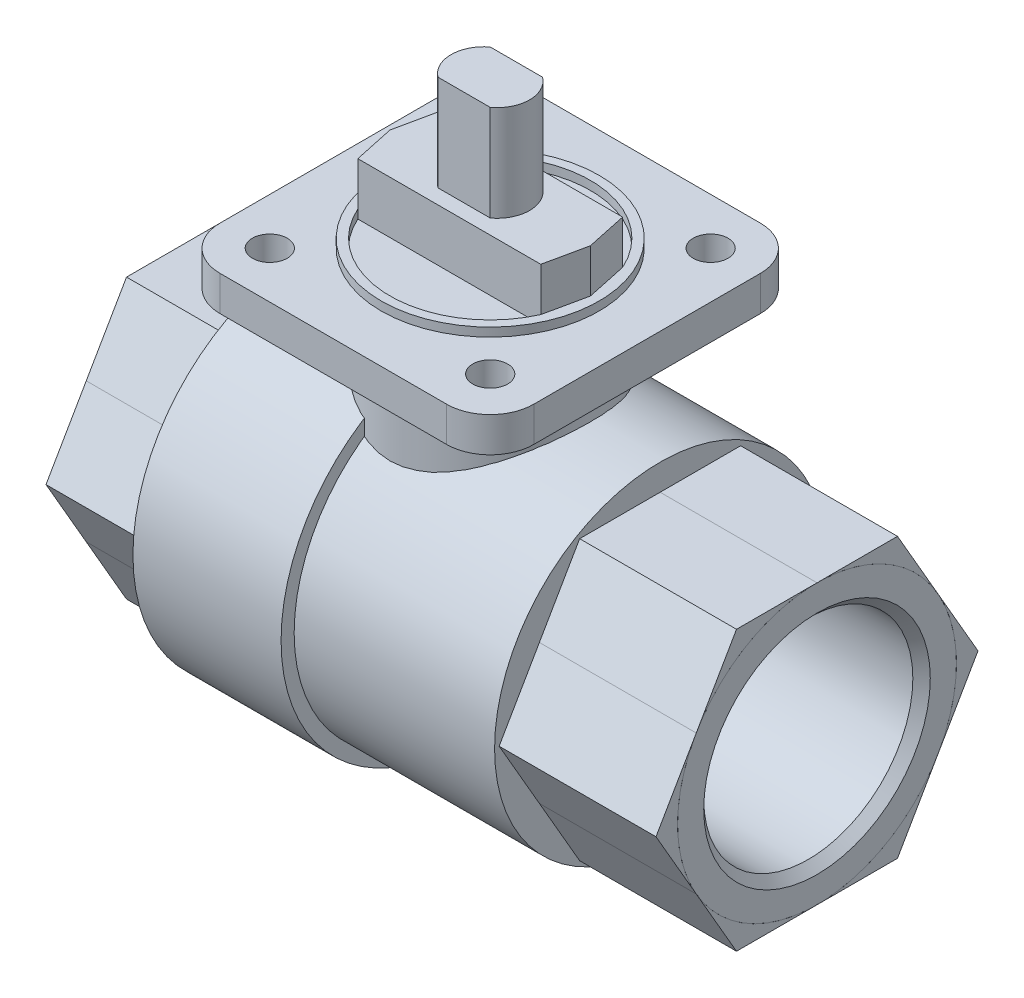
SolidWorks part; units mm, degrees
ref_plane "Front Plane" through (0, 0, 0) normal (0, 0, 1) x (1, 0, 0)
ref_plane "Top Plane" through (0, 0, 0) normal (0, 1, 0) x (1, 0, 0)
ref_plane "Right Plane" through (0, 0, 0) normal (1, 0, 0) x (0, 0, -1)
sketch "Szkic1" plane through (0, 0, 0) normal (0, 0, 1) x (1, 0, 0)
  line L0 (0, 0) -> (0, 32)
  line L1 (0, 32) -> (17, 32)
  line L2 (17, 32) -> (17, 0)
  line L3 (17, 0) -> (0, 0)
  line L4 (17, 32) -> (17, 30)
  line L5 (17, 0) -> (17, 2)
  line L6 (17, 2) -> (47, 2)
  line L7 (47, 2) -> (47, 30)
  line L8 (47, 30) -> (17, 30)
  line L9 (47, 30) -> (47, 32)
  line L10 (47, 32) -> (70, 32)
  line L11 (70, 32) -> (70, 0)
  line L12 (70, 0) -> (47, 0)
  line L13 (47, 0) -> (47, 2)
  line L14 (47, 2) -> (47, 0)
  line L15 (47, 2) -> (47, 30)
  line L16 (17, 2) -> (17, 30)
  line L17 (17, 30) -> (47, 30)
  line L18 (47, 2) -> (17, 2)
  line L19 (47, 2) -> (47, 0)
  line L20 (70, 0) -> (70, 32)
  line L21 (47, 32) -> (47, 30)
  line L22 (47, 32) -> (47, 30)
  line L23 (0, 32) -> (12, 32)
  line L24 (0, 0) -> (11, 0)
  line L25 (0, 32) -> (0, 28)
  line L26 (0, 28) -> (70, 28)
  line L27 (0, 0) -> (0, 4)
  line L28 (0, 4) -> (70, 4)
  line L29 (12, 32) -> (12, 36.5)
  line L30 (12, 36.5) -> (29, 36.5)
  line L31 (0, 16) -> (70, 16)
  line L32 (29, 36.5) -> (29, 35)
  line L33 (29, 35) -> (52, 35)
  line L34 (52, 35) -> (52, 32)
  line L35 (17, 30) -> (17, 26)
  line L36 (17, 26) -> (47, 26)
  line L37 (47, 26) -> (47, 30)
  dimension "D1" = 32
  dimension "D2" = 17
  dimension "D3" = 2
  dimension "D4" = 2
  dimension "D5" = 30
  dimension "D6" = 18
  dimension "D7" = 12
  dimension "D8" = 4
  dimension "D9" = 4
  dimension "D10" = 4.5
  dimension "D11" = 17
  dimension "D12" = 1.5
  dimension "D13" = 23
  dimension "D14" = 70
  dimension "D15" = 4
revolve "Obrót2" add sketch "Szkic1" angle 360 about L31 region at (8.5, 30, 0) region at (32, 27, 0) region at (32, 29, 0) region at (30.573, 33.0493, 0) region at (58.5, 30, 0)
sketch "Szkic2" plane through (0, 0, 0) normal (1, 0, 0) x (0, 0, -1)
  line L1 (18.4752, 16) -> (9.2376, 32)
  line L2 (9.2376, 32) -> (-9.2376, 32)
  line L3 (-9.2376, 32) -> (-18.4752, 16)
  line L4 (-18.4752, 16) -> (-9.2376, 0)
  line L5 (-9.2376, 0) -> (9.2376, 0)
  line L6 (9.2376, 0) -> (18.4752, 16)
  circle A0 centre (0, 16) radius 16
  circle A1 centre (0, 16) radius 16 construction
  dimension "D1" = 16
extrude "Dodanie-wyciągnięcie2" add sketch "Szkic2" along normal blind 70 separate body contours A0 L2 L3 | A0 L3 L4 | A0 L4 L5 | A0 L5 L6 | A0 L6 L1 | A0 L1 L2 region at (0, 16, -16.537) region at (0, 30.3215, -8.2685) region at (0, 1.6785, -8.2685) region at (0, 30.3215, 8.2685) region at (0, 1.6785, 8.2685) region at (0, 16, 16.537)
fillet "Zaokrąglenie2" radius 1 1 edges at (0, 16, 12)
chamfer "Sfazowanie1" distance 1 angle 45 1 edges at (70, 16, 12)
sketch "Szkic5" plane through (0, 0, 0) normal (0, 1, 0) x (1, 0, 0)
  line L0 (0, 0) -> (21, 0)
  line L1 (47, 0) -> (17, 0) construction
  line L2 (21, 0) -> (32.5, 0)
  line L3 (32.5, 0) -> (14.5, 0)
  line L4 (14.5, 18) -> (19.5, 18)
  line L6 (14.5, 0) -> (14.5, 18)
  line L7 (14.5, 18) -> (32.5, 18)
  line L8 (32.5, 18) -> (32.5, 0)
  line L9 (14.5, 18) -> (50.5, 18)
  line L10 (14.5, 18) -> (14.5, -18)
  line L11 (14.5, -18) -> (50.5, -18)
  line L12 (50.5, 18) -> (50.5, -18)
  line L13 (14.5, 18) -> (14.5, 13)
  line L14 (50.5, 18) -> (45.5, 18)
  line L15 (50.5, 18) -> (50.5, 13)
  line L16 (14.5, -18) -> (14.5, -13)
  line L17 (14.5, -18) -> (19.5, -18)
  line L18 (50.5, -18) -> (45.5, -18)
  line L19 (50.5, -18) -> (50.5, -13)
  line L20 (19.5, 13) -> (32.5, 0)
  line L21 (45.5, 13) -> (19.5, -13)
  line L22 (45.5, -13) -> (32.5, 0)
  line L23 (45.5, -13) -> (45, -12.5)
  line L24 (45.5, 13) -> (45.1464, 12.6464)
  line L25 (19.5, 13) -> (19.8536, 12.6464)
  line L26 (19.5, -13) -> (19.8536, -12.6464)
  circle A0 centre (32.5, 0) radius 11.5
  arc A2 (14.5, 13) -> (19.5, 18) centre (19.5, 13) cw
  arc A3 (19.5, -18) -> (14.5, -13) centre (19.5, -13) cw
  arc A4 (50.5, -13) -> (45.5, -18) centre (45.5, -13) cw
  arc A5 (45.5, 18) -> (50.5, 13) centre (45.5, 13) cw
  circle A10 centre (19.8536, 12.6464) radius 2
  circle A11 centre (45.1464, 12.6464) radius 2
  circle A12 centre (45, -12.5) radius 2
  circle A13 centre (19.8536, -12.6464) radius 2
  dimension "D15" = 0.5
  dimension "D16" = 0.5
  dimension "D17" = 0.5
  dimension "D18" = 0.5
  dimension "D19" = 4
  dimension "D20" = 4
  dimension "D21" = 4
  dimension "D22" = 4
  dimension "D1" = 21
  dimension "D2" = 11.5
  dimension "D3" = 18
  dimension "D4" = 18
  dimension "D5" = 36
  dimension "D6" = 36
  dimension "D7" = 5
  dimension "D8" = 5
  dimension "D9" = 5
  dimension "D10" = 5
  dimension "D11" = 5
  dimension "D12" = 5
  dimension "D13" = 5
  dimension "D14" = 5
extrude "Dodanie-wyciągnięcie3" add sketch "Szkic5" along normal blind 10 and the other way blind 6 from offset 36.5 separate body contours A0
extrude "Dodanie-wyciągnięcie5" add sketch "Szkic5<12>" along normal blind 4 from offset 42.5 separate body contours A2 L6 L0 A0 L8 L7 | A5 L9 L8 A0 L0 L10 A3 L11 A4 L12 region at (14.7546, 0, -6.5) region at (17.75, 0, 0.5091)
sketch "Szkic5<12>" plane through (0, 0, 0) normal (0, 1, 0) x (1, 0, 0) same geometry as "Szkic5"
sketch "Szkic7" plane through (0, 0, 0) normal (0, 1, 0) x (1, 0, 0)
  line L0 (32.5, 0) -> (21, 0)
  line L1 (21, 0) -> (22.0017, 4.6941)
  line L2 (22.0017, 4.6941) -> (32.5, 4.6941)
  line L3 (32.5, 4.6941) -> (32.5, 0)
  line L5 (21, 0) -> (22.0017, -4.6941)
  line L6 (22.0017, -4.6941) -> (32.5, -4.6941)
  line L7 (32.5, -4.6941) -> (32.5, 0)
  line L9 (32.5, 4.6941) -> (42.9983, 4.6941)
  line L10 (42.9983, 4.6941) -> (44, 0)
  line L11 (44, 0) -> (32.5, 0)
  line L12 (32.5, -4.6941) -> (42.9983, -4.6941)
  line L13 (42.9983, -4.6941) -> (44, 0)
  line L14 (32.5, 0) -> (32.5, 3.0011)
  line L15 (32.5, 3.0011) -> (32.5, -2.9989)
  line L16 (32.5, -2.9989) -> (35.5, -2.9989)
  line L17 (35.5, -2.9989) -> (35.5, 3.0011)
  line L18 (35.5, 3.0011) -> (29.5, 3.0011)
  line L19 (29.5, 3.0011) -> (29.5, -2.9989)
  line L20 (29.5, -2.9989) -> (32.5, -2.9989)
  line L21 (32.5, 0) -> (28, 0)
  line L22 (28, 0) -> (37, 0)
  circle A0 centre (32.5, 0) radius 11.5 construction
  circle A1 centre (32.5, 0) radius 11.5 construction
  arc A2 (29.5, 3.0011) -> (29.5, -2.9989) centre (31.7744, 0.0011) ccw
  arc A3 (35.5, -2.9989) -> (35.5, 3.0011) centre (33.2883, 0.0011) ccw
  circle A4 centre (32.5, 0) radius 12.5
  circle A5 centre (32.5, 0) radius 11.5
  dimension "D6" = 25
  dimension "D1" = 3
  dimension "D2" = 3
  dimension "D3" = 6
  dimension "D4" = 4.5
  dimension "D5" = 9
extrude "Dodanie-wyciągnięcie6" add sketch "Szkic7" along normal blind 6 from offset 46.5 separate body contours A2 L18 L3 L2 L1 L0 L22 | A2 L22 L0 L5 L6 L7 L20 | A3 L16 L7 L12 L13 L11 | A3 L11 L10 L9 L3 L18 region at (25.9353, 0, 2.5872) region at (25.9342, 0, -2.5871) region at (39.0692, 0, -2.5891) region at (39.0681, 0, 2.5891)
extrude "Dodanie-wyciągnięcie7" add sketch "Szkic7<4>" along normal blind 17 from offset 46.5 contours L0 A2 L19 | L19 A2 L0 | L18 L19 L0 L3 | L19 L20 L7 L0 | L17 L18 L3 L11 | L16 L17 L11 L7 | L11 A3 L17 | L17 A3 L11 region at (28.8924, 0, -1.1626) region at (28.8925, 0, 1.1616) region at (31, 0, -1.5006) region at (31, 0, 1.4994) region at (34, 0, 1.4994) region at (34, 0, -1.5006) region at (36.1182, 0, -1.1638) region at (36.1181, 0, 1.1628)
sketch "Szkic7<4>" plane through (0, 0, 0) normal (0, 1, 0) x (1, 0, 0) same geometry as "Szkic7"
extrude "Dodanie-wyciągnięcie12" add sketch "Szkic7<7>" along normal blind 1 from offset 46.5 contours A4 A5 | L1 A5 | L5 A5 | L13 A5 | L10 A5 region at (21.4017, 0, -2.3682) region at (21.4017, 0, 2.3682) region at (43.5983, 0, -2.3682) region at (43.5983, 0, 2.3682) region at (20.3536, 0, 0)
sketch "Szkic7<7>" plane through (0, 0, 0) normal (0, 1, 0) x (1, 0, 0) same geometry as "Szkic7"
